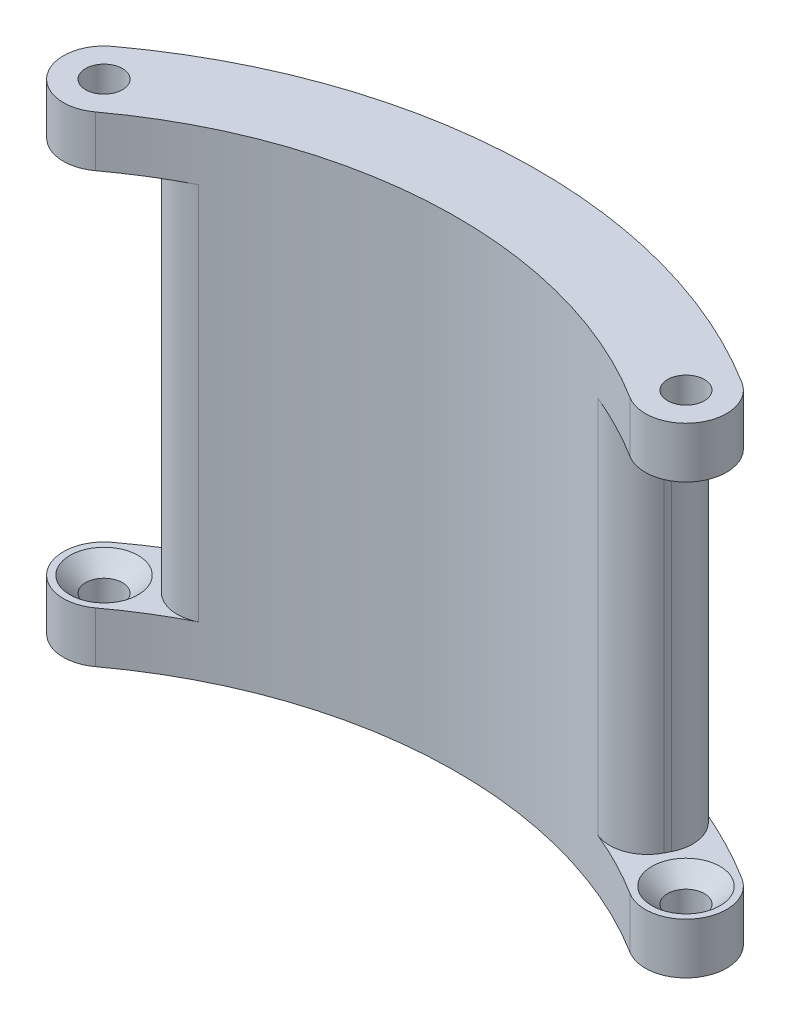
SolidWorks part; units mm, degrees
ref_plane "Front" through (0, 0, 0) normal (0, 0, 1) x (1, 0, 0)
ref_plane "Top" through (0, 0, 0) normal (0, 1, 0) x (1, 0, 0)
ref_plane "Right" through (0, 0, 0) normal (1, 0, 0) x (0, 0, -1)
sketch "Sketch1" plane through (0, 0, 0) normal (0, 1, 0) x (1, 0, 0)
  arc A0 (-27.3313, 37) -> (24.3926, 39) centre (0, 0) cw construction
  arc A1 (-27.3313, -37) -> (24.3926, -39) centre (0, 0) ccw construction
  arc A2 (-29.5594, 40.0163) -> (26.3812, 42.1793) centre (0, 0) cw
  arc A3 (-29.5594, 40.0163) -> (-25.1032, 33.9837) centre (-27.3313, 37) ccw
  arc A4 (26.3812, 42.1793) -> (22.4041, 35.8207) centre (24.3926, 39) cw
  arc A5 (-25.1032, 33.9837) -> (22.4041, 35.8207) centre (0, 0) cw
  dimension "D1" = 46
  dimension "D4" = 3.75
  dimension "D2" = 74
  dimension "D3" = 78
extrude "Boss-Extrude1" add sketch "Sketch1" along normal blind 4.699
hole_wizard "CSK for M3 Flat Head Machine Screw1" positions "Sketch2" profile "Sketch3" countersink size "M3" standard "ANSI Metric" end condition through all
sketch "Sketch2" plane through (0, 4.699, 0) normal (0, 1, 0) x (1, 0, 0)
  point P0 (-27.3313, 37)
  point P3 (24.3926, 39)
sketch "Sketch3" plane through (-27.3313, 4.699, -37) normal (1, 0, 0) x (0, 0, 1)
  line L0 (0, 0) -> (0, 4.699)
  line L1 (0, 4.699) -> (1.7, 4.699)
  line L2 (1.7, 4.699) -> (1.7, 1.45)
  line L3 (1.7, 1.45) -> (3.15, 0)
  line L5 (3.15, 0) -> (0, 0)
  line L6 (-1.7, 1.45) -> (-3.15, 0) construction
  line L11 (0, -6.35) -> (0, 107.95) construction
  dimension "Thru Hole Dia." = 3.4
  dimension "Thru Hole Depth" = 4.699
  dimension "Near C'Sink Dia." = 6.3
  dimension "Near C'Sink Angle" = 90
sketch "Sketch4" plane through (0, 4.699, 0) normal (0, 1, 0) x (1, 0, 0)
  line L0 (-22.053, 36.0379) -> (-25.9677, 42.4351)
  line L1 (19.2044, 37.6331) -> (22.6135, 44.3136)
  arc A0 (22.6135, 44.3136) -> (-25.9677, 42.4351) centre (0, 0) ccw
  arc A1 (26.3812, 42.1793) -> (-29.5594, 40.0163) centre (0, 0) ccw construction
  arc A2 (-22.053, 36.0379) -> (19.2044, 37.6331) centre (0, 0) cw
  arc A3 (22.4041, 35.8207) -> (-25.1032, 33.9837) centre (0, 0) ccw construction
  arc A4 (22.4041, 35.8207) -> (26.3812, 42.1793) centre (24.3926, 39) ccw construction
  circle A5 centre (-27.3313, 37) radius 1.7 construction
  dimension "D1" = 4
  dimension "D2" = 4
extrude "Boss-Extrude2" add sketch "Sketch4" along normal offset from surface (17.476 mm away) 22.175 up to face at (-27.3313, 0, -35.3)
mirror "Mirror1" about plane through (12.1963, 22.175, -19.5) normal (0, -1, 0) of "CSK for M3 Flat Head Machine Screw1", "Boss-Extrude2", "Boss-Extrude1"
fillet "Fillet1" radius 3.5 4 edges at (-22.053, 22.175, -36.0379) (-25.9677, 22.175, -42.4351) (19.2044, 22.175, -37.6331) (22.6135, 22.175, -44.3136)
equation "\"D1@Boss-Extrude2\"=44.35mm/2"
